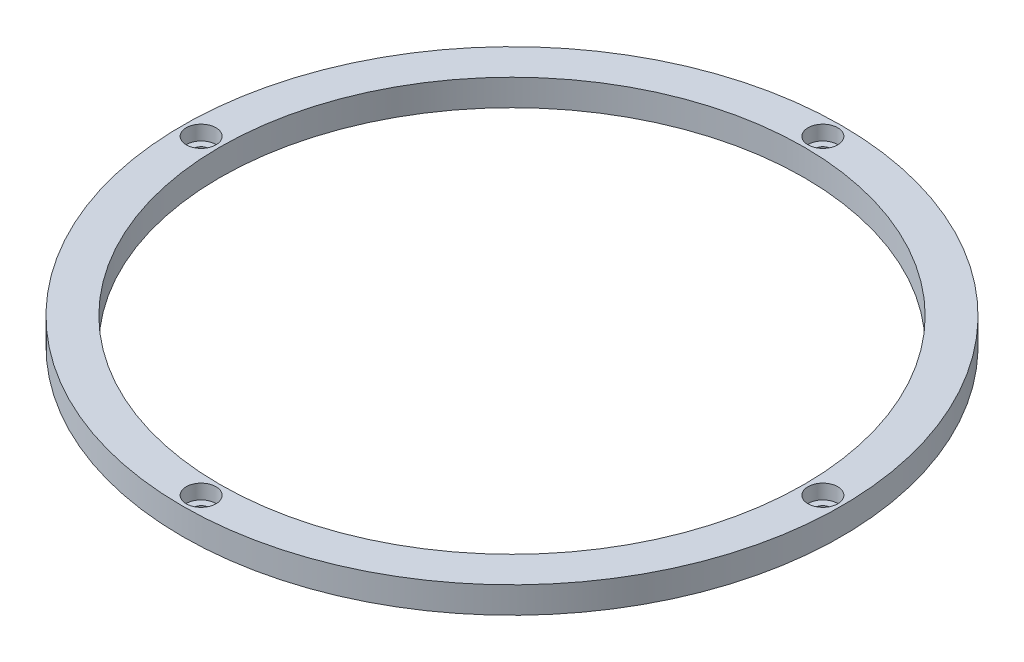
SolidWorks part; units mm, degrees
ref_plane "Front" through (0, 0, 0) normal (0, 0, 1) x (1, 0, 0)
ref_plane "Top" through (0, 0, 0) normal (0, 1, 0) x (1, 0, 0)
ref_plane "Right" through (0, 0, 0) normal (1, 0, 0) x (0, 0, -1)
sketch "Sketch1" plane through (0, 0, 0) normal (0, 1, 0) x (1, 0, 0)
  circle A0 centre (0, 0) radius 70.2564
  circle A1 centre (0, 0) radius 79.248
  dimension "D1" = 158.496
  dimension "D2" = 140.5128
extrude "Extrude2" add sketch "Sketch1" along normal blind 6.35
ref_point "Point1"
ref_axis "Axis1" through (0, 77.7958, 0) along (0, -1, 0)
hole_wizard "CBORE for #6 Socket Head Cap Screw1" positions "3DSketch2" profile "Sketch3" counterbore size "#6" standard "Ansi Inch" end condition through all
sketch3d "3DSketch2"
  line L2 (0, 6.35, -74.7522) -> (0, 6.35, 0) construction
  line L3 (0, 6.35, 0) -> (0, 0, 0) construction
  line L4 (0, 6.35, 0) -> (0, 0, 0) construction
  line L9 (-74.7522, 6.35, 0) -> (0, 6.35, 0) construction
  line L11 (0, 6.35, 0) -> (74.7522, 6.35, 0) construction
  line L13 (0, 6.35, 0) -> (0, 6.35, 74.7522) construction
  point P24 (0, 6.35, -74.7522)
  point P38 (0, 6.35, 74.7522)
  point P40 (74.7522, 6.35, 0)
  point P42 (-74.7522, 6.35, 0)
  dimension "D1" = 74.7522
  dimension "D2" = 74.7522
  dimension "D3" = 74.7522
  dimension "D4" = 74.7522
sketch "Sketch3" plane through (0, 6.35, -74.7522) normal (1, 0, 0) x (0, 0, 1)
  line L0 (0, 0) -> (0, 6.35)
  line L1 (0, 6.35) -> (1.8986, 6.35)
  line L3 (1.8986, 6.35) -> (1.8986, 3.5052)
  line L4 (1.8986, 3.5052) -> (3.5725, 3.5052)
  line L5 (3.5725, 3.5052) -> (3.5725, 0)
  line L7 (3.5725, 0) -> (0, 0)
  line L11 (0, -6.35) -> (0, 107.95) construction
  dimension "Thru Hole Dia." = 3.7973
  dimension "Thru Hole Depth" = 6.35
  dimension "C'Bore Dia." = 7.145
  dimension "C'Bore Depth" = 3.5052
